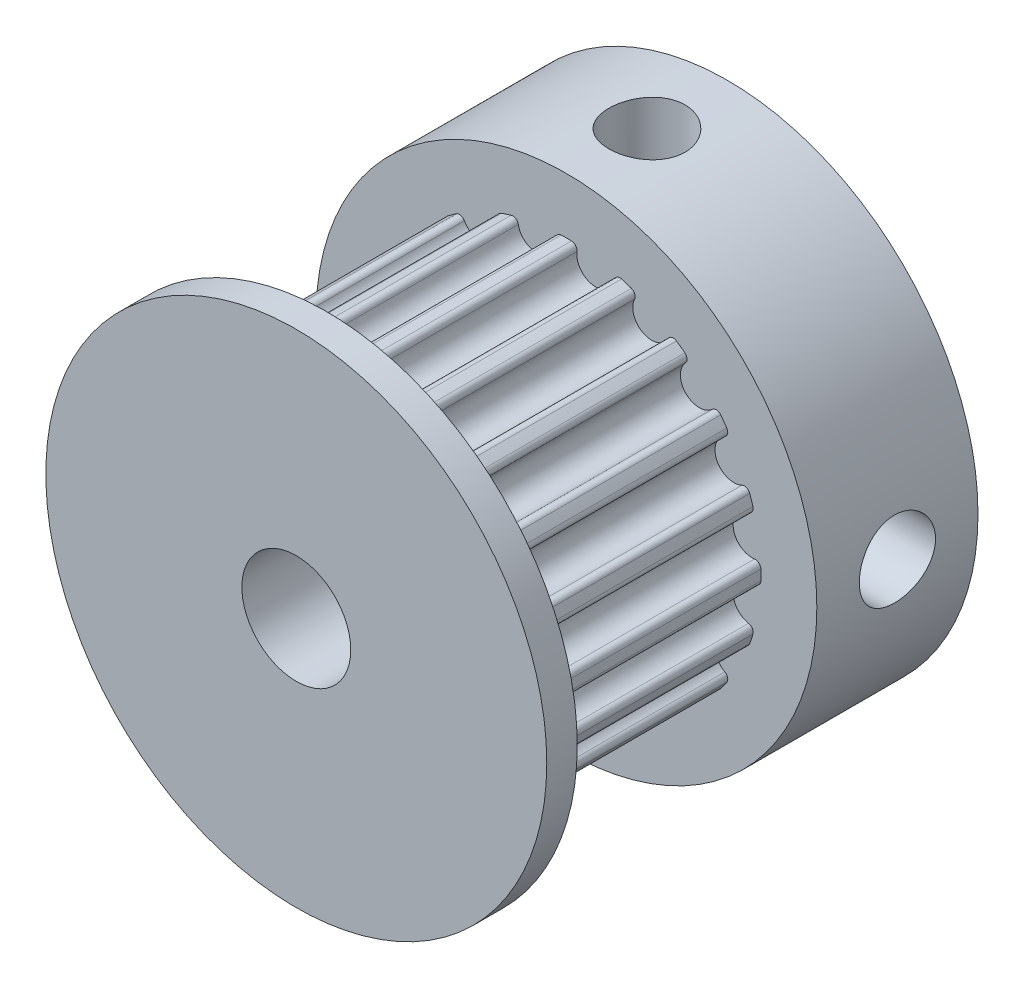
SolidWorks part; units mm, degrees
ref_plane "Front Plane" through (0, 0, 0) normal (1, 0, 0) x (0, 1, 0)
ref_plane "Top Plane" through (0, 0, 0) normal (0, 0, 1) x (0, 1, 0)
ref_plane "Right Plane" through (0, 0, 0) normal (0, 1, 0) x (-1, 0, 0)
other "Configuration Table"
sketch "Sketch2" plane through (0, 0, 0) normal (0, 0, 1) x (0, 1, 0)
  line L0 (0, 0) -> (0, 8.9343)
  line L1 (0, 0) -> (1.2146, 7.6687) construction
  line L2 (1.2146, 7.6687) -> (1.3507, 8.528) construction
  line L3 (0, 0) -> (2.7608, 8.497)
  arc A3 (0.572, 8.916) -> (2.2112, 8.6563) centre (1.3507, 8.528) ccw
  arc A4 (0, 8.9343) -> (0.572, 8.916) centre (0, 0) cw
  arc A5 (2.2112, 8.6563) -> (2.7608, 8.497) centre (0, 0) cw
  dimension "D1" = 8.9343
  dimension "D2" = 7.7643
  dimension "D3" = 9
  dimension "D4" = 0.87
  dimension "D5" = 8.9343
  dimension "D6" = 9
extrude "Boss-Extrude1" add sketch "Sketch2" along normal blind 11 contours A5 A3 A4 L0 L3 region at (-5.4794, 0.8679, 0)
fillet "Fillet2" radius 0.26 2 edges at (-8.6563, 2.2112, 5.5) (-8.916, 0.572, 5.5)
pattern_circular "CirPattern12" count 20 over 360 about axis through (0, 0, 11) along (0, 0, -1) of "Fillet2", "Boss-Extrude1"
sketch "Sketch3" plane through (0, 0, 0) normal (0, 0, 1) x (0, 1, 0)
  circle A0 centre (0, 0) radius 11.5
  circle A1 centre (0, 0) radius 2.5
  dimension "D1" = 23
  dimension "D2" = 5
extrude "Boss-Extrude2" add sketch "Sketch3" against normal blind 7.4 contours A1 | A0 A1 region at (0, -11.1747, 0) region at (0, 0, 0)
extrude "Boss-Extrude3" add sketch "Sketch3<3>" along normal blind 1.4 from surface contours A1 | A0 A1 region at (0, -11.1747, 0) region at (0, 0, 0) starting at face at (0, 0, 11)
sketch "Sketch3<3>" plane through (0, 0, 0) normal (0, 0, 1) x (0, 1, 0) same geometry as "Sketch3"
extrude "Cut-Extrude1" cut sketch "Sketch3<4>" against normal through all both and the other way through all contours A1 region at (0, 0, 0)
sketch "Sketch3<4>" plane through (0, 0, 0) normal (0, 0, 1) x (0, 1, 0) same geometry as "Sketch3"
ref_plane "Plane1" through (11.5, 0, 0) normal (1, 0, 0) x (0, 0, -1)
ref_plane "Plane2" through (0, 11.5, 0) normal (0, 1, 0) x (0, 0, 1)
sketch "Sketch4" plane through (11.5, 0, 0) normal (1, 0, 0) x (0, 0, -1)
  line L0 (0, 11.5) -> (0, -11.5) construction
  line L1 (0, 11.5) -> (0, -11.5)
  line L2 (7.4, -11.5) -> (7.4, 11.5) construction
  line L3 (7.4, -11.5) -> (7.4, 11.5)
  line L4 (7.4, 0) -> (0, 0) construction
  circle A0 centre (3.7, 0) radius 1.75
  dimension "D1" = 3.5
sketch "Sketch5" plane through (0, 11.5, 0) normal (0, 1, 0) x (0, 0, 1)
  line L0 (0, -11.5) -> (0, 11.5) construction
  line L1 (-7.4, 11.5) -> (-7.4, -11.5) construction
  line L2 (0, -11.5) -> (0, 11.5)
  line L3 (-7.4, 11.5) -> (-7.4, -11.5)
  line L4 (-7.4, 0) -> (0, 0) construction
  circle A0 centre (-3.7, 0) radius 1.75
  dimension "D1" = 3.5
extrude "Cut-Extrude2" cut sketch "Sketch4" against normal up to vertex (11.5 mm away) and the other way through all contours A0 up to point (0, 0, 0)
extrude "Cut-Extrude3" cut sketch "Sketch5" against normal up to vertex (11.5 mm away) contours A0 up to point (0, 0, 0)
equation "\"Pitch\"= 3mm"
equation "\"Teeth\"= 20"
equation "\"Shaft\"= 5mm"
equation "\"BeltHeight\"= 10 + 1"
equation "\"PitchDiameter\"= \"Pitch\" * \"Teeth\" / PI * 1mm"
equation "\"D1@Sketch2\"=\"PitchDiameter\"/2 - 0.615"
equation "\"D2@Sketch2\"=\"D1@Sketch2\"-1.17"
equation "\"D3@Sketch2\"= 180 / \"Teeth\""
equation "\"D1@Boss-Extrude1\"=\"BeltHeight\""
equation "\"D5@Sketch2\"=\"D1@Sketch2\""
equation "\"D6@Sketch2\"=\"D3@Sketch2\""
equation "\"D1@CirPattern12\"=\"Teeth\""
equation "\"Diameter\"= 23mm"
equation "\"D1@Sketch3\"=\"Diameter\""
equation "\"D2@Sketch3\"=\"Shaft\""
